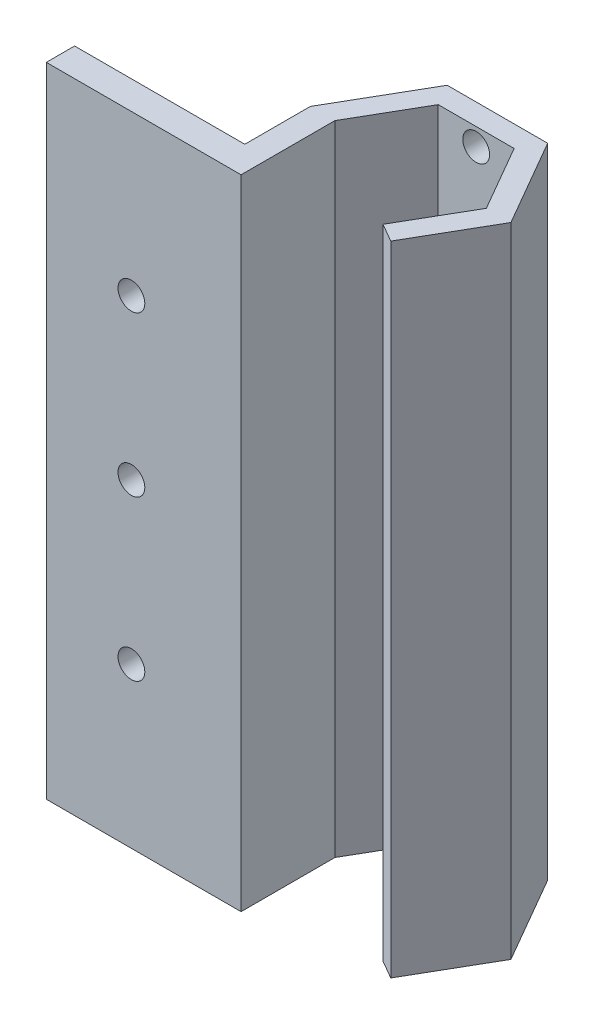
SolidWorks part; units mm, degrees
ref_plane "Front Plane" through (0, 0, 0) normal (0, 0, 1) x (1, 0, 0)
ref_plane "Top Plane" through (0, 0, 0) normal (0, 1, 0) x (1, 0, 0)
ref_plane "Right Plane" through (0, 0, 0) normal (1, 0, 0) x (0, 0, -1)
sketch "Sketch4" plane through (0, 0, 0) normal (0, 1, 0) x (1, 0, 0)
  line L0 (8.9489, -15.4) -> (17.8401, 0)
  line L1 (8.8623, 15.35) -> (-8.8623, 15.35) construction
  line L2 (-8.8623, 15.35) -> (-17.7247, 0) construction
  line L3 (-17.7247, 0) -> (-8.8623, -15.35) construction
  line L4 (-8.8623, -15.35) -> (8.8623, -15.35) construction
  line L5 (8.8623, -15.35) -> (17.7247, 0) construction
  line L6 (17.7247, 0) -> (8.8623, 15.35) construction
  line L7 (17.8401, 0) -> (8.9201, 15.45)
  line L8 (8.9201, 15.45) -> (-8.9201, 15.45)
  line L9 (-8.9201, 15.45) -> (-17.8113, 0.05)
  line L10 (13.2791, -17.9) -> (23.6136, 0)
  line L11 (23.6136, 0) -> (11.8068, 20.45)
  line L12 (11.8068, 20.45) -> (-11.8068, 20.45)
  line L16 (8.9489, -15.4) -> (13.2791, -17.9)
  line L30 (-17.8113, 0.05) -> (-17.8113, -22)
  line L33 (-23.5848, 0.05) -> (-23.5848, -15.35)
  line L35 (-11.8068, 20.45) -> (-23.5848, 0.05)
  line L36 (-11.8068, 20.45) -> (-22.1414, 2.55) construction
  line L39 (-23.5848, -15.35) -> (-63.5848, -15.35)
  line L40 (-63.5848, -22) -> (-63.5848, -15.35)
  line L41 (-63.5848, -22) -> (-17.8113, -22)
  circle A0 centre (0, 0) radius 15.35 construction
  dimension "D2" = 0.1
  dimension "D1" = 30.7
  dimension "D3" = 5.1
  dimension "D4" = 6.65
  dimension "D5" = 22.05
  dimension "D6" = 40
  dimension "D7" = 15.4
  dimension "D8" = 20.4
extrude "Boss-Extrude3" add sketch "Sketch4" against normal blind 150 contours L39 L40 L41 L30 L9 L8 L7 L0 L16 L10 L11 L12 L35 L33
sketch "Sketch5" plane through (0, 0, 15.35) normal (0, 0, -1) x (-1, 0, 0)
  line L0 (43.5848, 0) -> (43.5848, -150) construction
  line L1 (23.5848, 0) -> (63.5848, 0) construction
  line L2 (23.5848, -150) -> (63.5848, -150) construction
  line L3 (63.5848, -75) -> (23.5848, -75) construction
  line L4 (63.5848, -150) -> (63.5848, 0) construction
  line L5 (23.5848, -150) -> (23.5848, 0) construction
  line L6 (23.5848, -75) -> (23.5848, -150) construction
  line L7 (23.5848, -75) -> (23.5848, 0) construction
  line L8 (23.5848, -112.5) -> (63.5848, -112.5) construction
  line L9 (23.5848, -37.5) -> (63.5848, -37.5) construction
  circle A0 centre (43.5848, -37.5) radius 3.15
  circle A1 centre (43.5848, -75) radius 3.15
  circle A2 centre (43.5848, -112.5) radius 3.15
extrude "Cut-Extrude1" cut sketch "Sketch5" against normal blind 10 contours A0 | A1 | A2
sketch "Sketch6" plane through (0, 0, -20.45) normal (0, 0, -1) x (-1, 0, 0)
  line L0 (0, 0) -> (0, -150) construction
  line L2 (-11.8068, -150) -> (11.8068, -150) construction
  line L4 (0, 0) -> (0, -1) construction
  line L5 (0, -7.3) -> (0, -25.7) construction
  line L7 (0, -150) -> (0, -149) construction
  circle A2 centre (0, -4.15) radius 3.15
  circle A3 centre (0, -145.85) radius 3.15
  point P12 (0, 0)
  dimension "D1" = 1
  dimension "D2" = 6.3
  dimension "D4" = 6.3
  dimension "D3" = 1
  dimension "D5" = 18.4
extrude "Cut-Extrude3" cut sketch "Sketch6" against normal blind 10 contours A3 | A2
sketch "Sketch7" plane through (0, 0, -20.45) normal (0, 0, -1) x (-1, 0, 0)
  line L0 (0, -7.3) -> (0, -25.7) construction
  line L1 (-11.8068, -25.7) -> (11.8068, -25.7)
  line L2 (-11.8068, -150) -> (-11.8068, 0) construction
  line L3 (11.8068, -150) -> (11.8068, 0) construction
  line L4 (11.8068, -25.7) -> (11.8068, -27.2933)
  line L5 (11.8068, -27.2933) -> (-11.8068, -27.2933)
  line L6 (-11.8068, -27.2933) -> (-11.8068, -25.7)
  line L7 (0, -142.7) -> (0, -124.3) construction
  line L8 (-11.8068, -124.3) -> (11.8068, -124.3)
  line L9 (11.8068, -124.3) -> (11.8068, -120.4489)
  line L10 (11.8068, -120.4489) -> (-11.8068, -120.4489)
  line L11 (-11.8068, -120.4489) -> (-11.8068, -124.3)
  circle A0 centre (0, -4.15) radius 3.15 construction
  circle A1 centre (0, -145.85) radius 3.15 construction
  dimension "D1" = 18.4
  dimension "D2" = 18.4
extrude "Boss-Extrude4" add sketch "Sketch7" against normal blind 10
